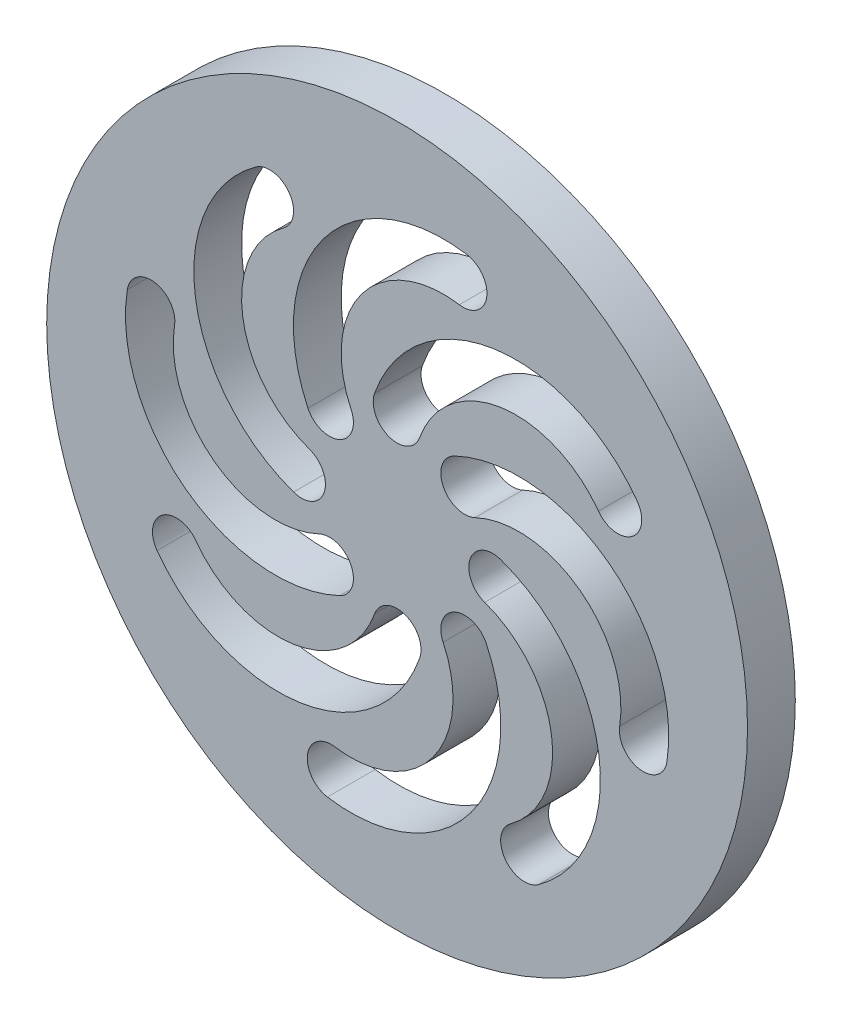
SolidWorks part; units mm, degrees
ref_plane "Front Plane" through (0, 0, 0) normal (0, 0, 1) x (1, 0, 0)
ref_plane "Top Plane" through (0, 0, 0) normal (0, 1, 0) x (1, 0, 0)
ref_plane "Right Plane" through (0, 0, 0) normal (1, 0, 0) x (0, 0, -1)
sketch "Sketch1" plane through (0, 0, 0) normal (0, 0, 1) x (1, 0, 0)
  line L0 (0, 60.505) -> (0, -60.505) construction
  line L1 (-16.0502, -9.2666) -> (16.0502, 9.2666) construction
  line L2 (0, 0) -> (0, 9.525) construction
  line L3 (0, 0) -> (6.7352, 6.7352) construction
  line L4 (0, 9.525) -> (0, 34.925) construction
  circle A0 centre (0, 0) radius 34.925
  arc A1 (2.2439, 8.7279) -> (-2.2439, 10.3221) centre (0, 9.525) cw
  arc A2 (-2.2439, 10.3221) -> (23.9239, 14.0991) centre (11.8344, 5.3212) cw
  arc A3 (23.9239, 14.0991) -> (20.0701, 11.3009) centre (21.997, 12.7) cw
  arc A4 (20.0701, 11.3009) -> (2.2439, 8.7279) centre (11.8344, 5.3212) ccw
  arc A5 (5.7121, 8.8855) -> (26.8863, -6.9472) centre (12.1309, -4.6055) cw
  arc A6 (7.7582, 4.5849) -> (5.7121, 8.8855) centre (6.7352, 6.7352) cw
  arc A7 (22.1827, -6.2008) -> (7.7582, 4.5849) centre (12.1309, -4.6055) ccw
  arc A8 (26.8863, -6.9472) -> (22.1827, -6.2008) centre (24.5345, -6.574) cw
  arc A9 (10.3221, 2.2439) -> (14.0991, -23.9239) centre (5.3212, -11.8344) cw
  arc A10 (8.7279, -2.2439) -> (10.3221, 2.2439) centre (9.525, 0) cw
  arc A11 (11.3009, -20.0701) -> (8.7279, -2.2439) centre (5.3212, -11.8344) ccw
  arc A12 (14.0991, -23.9239) -> (11.3009, -20.0701) centre (12.7, -21.997) cw
  arc A13 (8.8855, -5.7121) -> (-6.9472, -26.8863) centre (-4.6055, -12.1309) cw
  arc A14 (4.5849, -7.7582) -> (8.8855, -5.7121) centre (6.7352, -6.7352) cw
  arc A15 (-6.2008, -22.1827) -> (4.5849, -7.7582) centre (-4.6055, -12.1309) ccw
  arc A16 (-6.9472, -26.8863) -> (-6.2008, -22.1827) centre (-6.574, -24.5345) cw
  arc A25 (2.2439, -10.3221) -> (-23.9239, -14.0991) centre (-11.8344, -5.3212) cw
  arc A26 (-2.2439, -8.7279) -> (2.2439, -10.3221) centre (0, -9.525) cw
  arc A27 (-20.0701, -11.3009) -> (-2.2439, -8.7279) centre (-11.8344, -5.3212) ccw
  arc A28 (-23.9239, -14.0991) -> (-20.0701, -11.3009) centre (-21.997, -12.7) cw
  arc A29 (-5.7121, -8.8855) -> (-26.8863, 6.9472) centre (-12.1309, 4.6055) cw
  arc A30 (-7.7582, -4.5849) -> (-5.7121, -8.8855) centre (-6.7352, -6.7352) cw
  arc A31 (-22.1827, 6.2008) -> (-7.7582, -4.5849) centre (-12.1309, 4.6055) ccw
  arc A32 (-26.8863, 6.9472) -> (-22.1827, 6.2008) centre (-24.5345, 6.574) cw
  arc A33 (-10.3221, -2.2439) -> (-14.0991, 23.9239) centre (-5.3212, 11.8344) cw
  arc A34 (-8.7279, 2.2439) -> (-10.3221, -2.2439) centre (-9.525, 0) cw
  arc A35 (-11.3009, 20.0701) -> (-8.7279, 2.2439) centre (-5.3212, 11.8344) ccw
  arc A36 (-14.0991, 23.9239) -> (-11.3009, 20.0701) centre (-12.7, 21.997) cw
  arc A37 (-8.8855, 5.7121) -> (6.9472, 26.8863) centre (4.6055, 12.1309) cw
  arc A38 (-4.5849, 7.7582) -> (-8.8855, 5.7121) centre (-6.7352, 6.7352) cw
  arc A39 (6.2008, 22.1827) -> (-4.5849, 7.7582) centre (4.6055, 12.1309) ccw
  arc A40 (6.9472, 26.8863) -> (6.2008, 22.1827) centre (6.574, 24.5345) cw
  point P6 (0, 0)
  point P17 (0, 0)
  point P77 (0, 0)
  dimension "D1" = 9.525
  dimension "D3" = 60
  dimension "D4" = 25.4
  dimension "D2" = 2.3813
  dimension "D7" = 25.4
  dimension "D5" = 8
extrude "Boss-Extrude1" add sketch "Sketch1" along normal blind 4.7625
ref_axis "Axis1" through (0, 0, 0) along (0, 0, 1)
equation "\"slot-end-angle\"=60"
equation "\"D3@Sketch1\"=\"slot-end-angle\""
equation "\"slot-spacing-angle\"=60"
equation "\"slot-gap\"=0.01"
equation "\"pulley-thickness\"=0.25"
equation "\"pin-diameter\"=2*\"slot-radius\"-2*\"slot-gap\""
equation "\"slot-radius\"=3/32"
equation "\"D2@Sketch1\"=\"slot-radius\""
equation "\"vert-line-length\"=2.0in"
equation "\"test\"=1"
equation "\"disc-thickness\"=0.1875in"
equation "\"D1@Boss-Extrude1\"=\"disc-thickness\""
equation "\"center-distance\"=0.375in"
equation "\"D1@Sketch1\"=\"center-distance\""
equation "\"slot-to-disc-OD\"=1.0in"
equation "\"D7@Sketch1\"=\"slot-to-disc-OD\""
equation "\"number-slots\"=8"
equation "\"D5@Sketch1\"=\"number-slots\""
